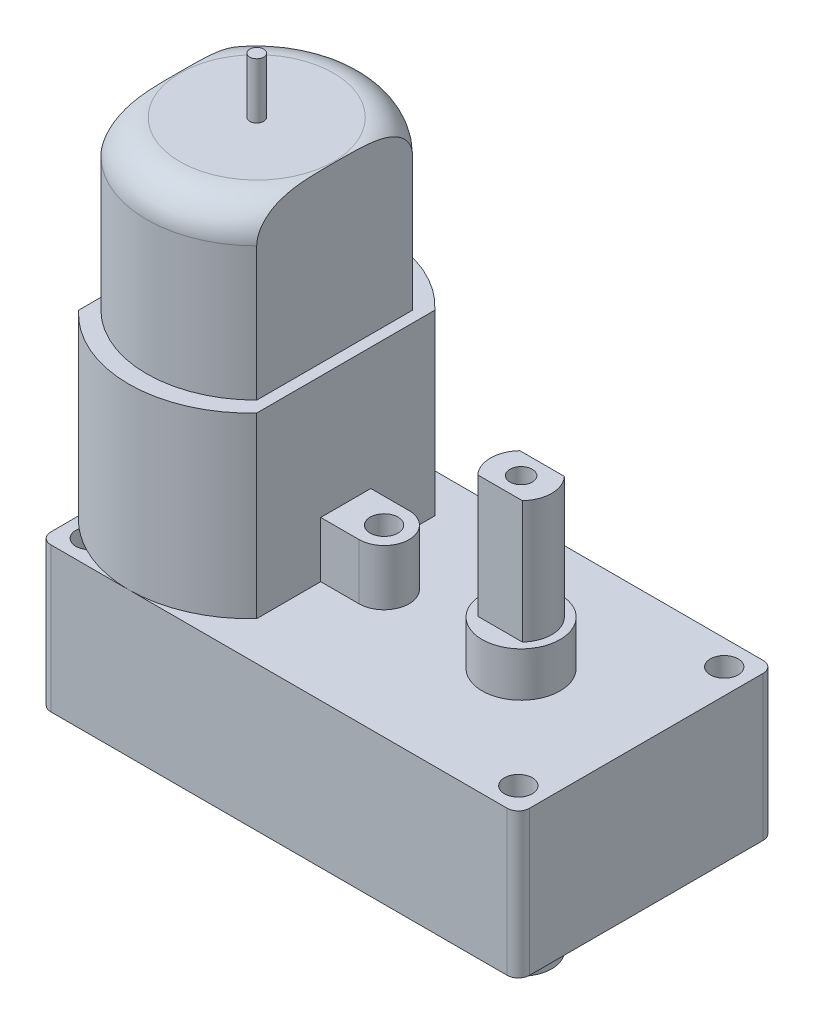
SolidWorks part; units mm, degrees
ref_plane "Front Plane" through (0, 0, 0) normal (0, 0, 1) x (1, 0, 0)
ref_plane "Top Plane" through (0, 0, 0) normal (0, 1, 0) x (1, 0, 0)
ref_plane "Right Plane" through (0, 0, 0) normal (1, 0, 0) x (0, 0, -1)
sketch "Sketch2" plane through (0, 0, 0) normal (0, 1, 0) x (1, 0, 0)
  line L0 (0, 20.75) -> (43, 20.75) construction
  line L1 (0, 0) -> (43, 0)
  line L2 (0, 0) -> (0, 23)
  line L3 (0, 23) -> (43, 23)
  line L4 (43, 0) -> (43, 23)
  line L5 (43, 20.75) -> (0, 2.25) construction
  line L6 (0, 2.25) -> (43, 2.25) construction
  line L7 (43, 2.25) -> (40.75, 0) construction
  line L8 (40.75, 0) -> (40.75, 23) construction
  line L9 (40.75, 23) -> (2.25, 23) construction
  line L10 (2.25, 23) -> (2.25, 0) construction
  circle A0 centre (2.25, 20.75) radius 1.25
  circle A1 centre (40.75, 20.75) radius 1.25
  circle A2 centre (40.75, 2.25) radius 1.25
  circle A3 centre (2.25, 2.25) radius 1.25
  dimension "D7" = 2.5
  dimension "D1" = 23
  dimension "D2" = 43
  dimension "D3" = 2.25
  dimension "D4" = 2.25
  dimension "D5" = 2.25
  dimension "D6" = 2.25
extrude "Boss-Extrude1" add sketch "Sketch2" along normal blind 13
fillet "Fillet1" radius 1 4 edges at (0, 6.5, -23) (43, 6.5, -23) (43, 6.5, 0) (0, 6.5, 0)
sketch "Sketch3" plane through (0, 13, 0) normal (0, 1, 0) x (1, 0, 0)
  line L2 (16, 19.5) -> (16, 3.5)
  line L4 (0, 19.5) -> (0, 3.5)
  line L5 (0, 19.5) -> (16, 19.5) construction
  line L6 (16, 19.5) -> (16, 3.5) construction
  line L7 (16, 3.5) -> (0, 3.5) construction
  arc A0 (0, 19.5) -> (16, 19.5) centre (8, 12.1071) cw
  arc A1 (0, 3.5) -> (16, 3.5) centre (8, 10.8929) ccw
extrude "Boss-Extrude2" add sketch "Sketch3" along normal blind 16
sketch "Sketch4" plane through (0, 29, 0) normal (0, 1, 0) x (1, 0, 0)
  line L0 (0, 18.5) -> (16, 18.5) construction
  line L1 (0, 19.5) -> (0, 3.5) construction
  line L2 (16, 3.5) -> (16, 19.5) construction
  line L3 (1, 20.4531) -> (15, 20.4531) construction
  line L4 (0, 4.5) -> (16, 4.5) construction
  line L5 (1, 20.4531) -> (1, 2.5469) construction
  line L6 (15, 20.4531) -> (1, 2.5469) construction
  line L7 (15, 20.4531) -> (15, 2.5469) construction
  line L8 (16, 3.5) -> (16, 19.5) construction
  line L9 (1, 2.5469) -> (15, 2.5469) construction
  line L10 (1, 18.5) -> (1, 4.5)
  line L11 (15, 18.5) -> (15, 4.5)
  arc A0 (16, 19.5) -> (0, 19.5) centre (8, 12.1071) ccw construction
  arc A1 (0, 3.5) -> (16, 3.5) centre (8, 10.8929) ccw construction
  arc A2 (1, 18.5) -> (15, 18.5) centre (8, 11.5) cw
  arc A3 (1, 4.5) -> (15, 4.5) centre (8, 11.5) ccw
  dimension "D1" = 1
  dimension "D2" = 1
  dimension "D3" = 1
  dimension "D4" = 1
extrude "Boss-Extrude3" add sketch "Sketch4" along normal blind 15
sketch "Sketch5" plane through (0, 44, 0) normal (0, 1, 0) x (1, 0, 0)
  circle A0 centre (8, 11.5) radius 0.625
  dimension "D1" = 1.25
extrude "Boss-Extrude4" add sketch "Sketch5" along normal blind 5
fillet "Fillet2" radius 3 2 edges at (8, 44, -21.3995) (8, 44, -1.6005)
sketch "Sketch6" plane through (0, 13, 0) normal (0, 1, 0) x (1, 0, 0)
  line L0 (31.75, 23) -> (31.75, 0) construction
  line L1 (42, 23) -> (8, 23) construction
  line L2 (8, 0) -> (42, 0) construction
  line L3 (31.75, 0) -> (43, 11.5) construction
  line L4 (43, 1) -> (43, 22) construction
  line L5 (43, 11.5) -> (22.8709, 11.5) construction
  circle A0 centre (31.75, 11.5) radius 3.5
  dimension "D1" = 11.25
extrude "Boss-Extrude5" add sketch "Sketch6" along normal blind 4
sketch "Sketch7" plane through (0, 17, 0) normal (0, 1, 0) x (1, 0, 0)
  line L2 (29.75, 13.3875) -> (33.75, 13.3875)
  line L3 (33.75, 9.6125) -> (29.75, 9.6125)
  arc A0 (29.75, 13.3875) -> (29.75, 9.6125) centre (31.75, 11.5) ccw
  arc A1 (33.75, 9.6125) -> (33.75, 13.3875) centre (31.75, 11.5) ccw
  circle A3 centre (31.75, 11.5) radius 1
  dimension "D1" = 4
  dimension "D2" = 5.5
  dimension "D3" = 2
extrude "Boss-Extrude7" add sketch "Sketch7" along normal blind 11
sketch "Sketch8" plane through (0, 13, 0) normal (0, 1, 0) x (1, 0, 0)
  line L0 (-1.5236, 11.5) -> (45.184, 11.5) construction
  line L1 (16, 15.5912) -> (16, 7.4078) construction
  line L2 (0, 19.5) -> (0, 3.5) construction
  line L7 (-3.4371, 13.75) -> (0, 13.75)
  line L10 (16, 3.5) -> (16, 19.5) construction
  line L11 (-3.4371, 9.25) -> (0, 9.25)
  line L12 (0, 13.75) -> (0, 9.25)
  line L14 (16, 9.25) -> (19.44, 9.25)
  line L15 (16, 13.75) -> (19.44, 13.75)
  line L19 (16, 13.75) -> (16, 9.25)
  arc A0 (-3.4371, 9.25) -> (-3.4371, 13.75) centre (-3.4371, 11.5) cw
  circle A1 centre (-3.4371, 11.5) radius 1.25
  arc A2 (19.44, 13.75) -> (19.44, 9.25) centre (19.44, 11.5) cw
  circle A3 centre (19.44, 11.5) radius 1.25
  point P4 (0, 11.5)
  point P16 (15.0032, 11.2608)
  dimension "D3" = 3.44
  dimension "D1" = 3.4371
  dimension "D2" = 4.5
  dimension "D4" = 3.44
  dimension "D5" = 4.5
  dimension "D6" = 4.5
  dimension "D7" = 2.25
  dimension "D8" = 2.25
extrude "Boss-Extrude8" add sketch "Sketch8" along normal blind 5
sketch "Sketch9" plane through (0, 0, 0) normal (0, -1, 0) x (1, 0, 0)
  line L2 (33.75, -13.3875) -> (29.75, -13.3875)
  line L3 (29.75, -9.6125) -> (33.75, -9.6125)
  circle A1 centre (18.877, -11.5) radius 1.4338 construction
  arc A3 (33.75, -13.3875) -> (33.75, -9.6125) centre (31.75, -11.5) ccw
  arc A4 (29.75, -9.6125) -> (29.75, -13.3875) centre (31.75, -11.5) ccw
extrude "Boss-Extrude9" add sketch "Sketch9" along normal blind 9
sketch "Sketch10" plane through (0, 0, 0) normal (0, -1, 0) x (1, 0, 0)
  line L0 (19.44, -11.5) -> (8, -11.5) construction
  line L1 (31.75, -11.5) -> (31.75, -20.3456) construction
  circle A0 centre (20.75, -11.5) radius 2
  dimension "D2" = 4
  dimension "D1" = 11
extrude "Boss-Extrude10" add sketch "Sketch10" along normal blind 2
